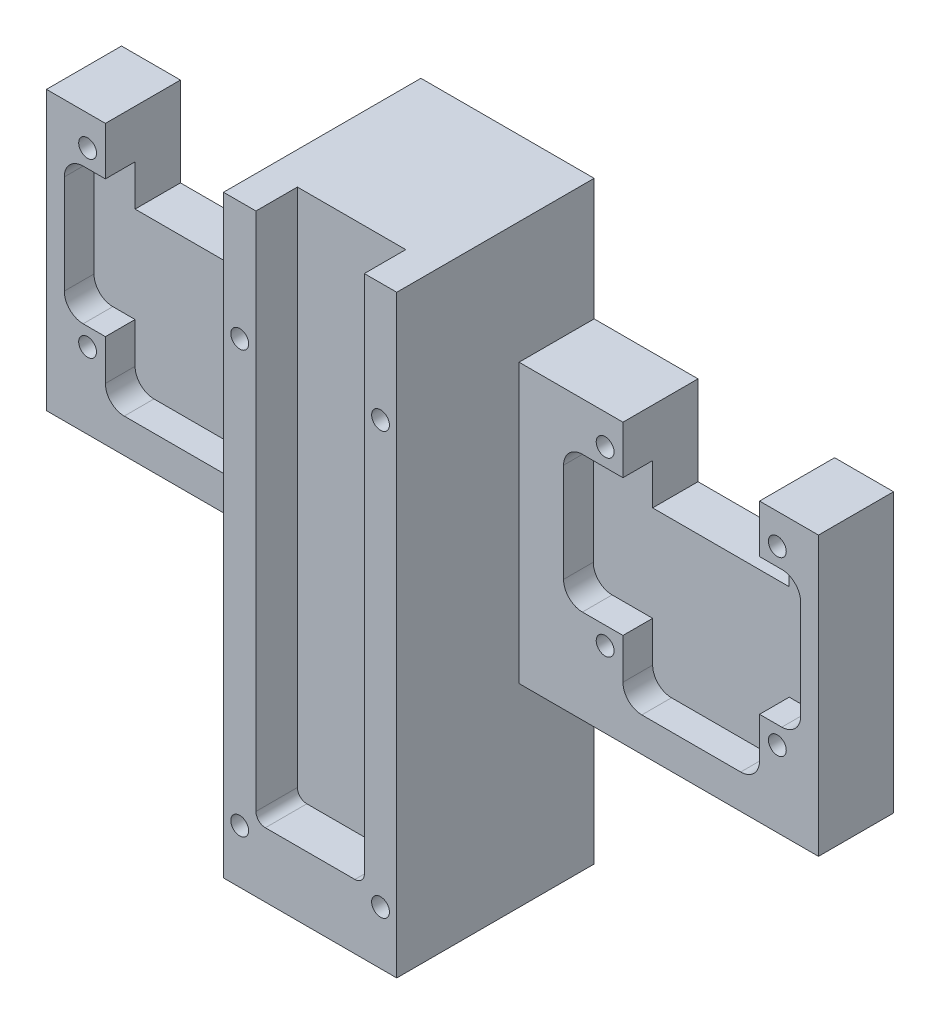
SolidWorks part; units mm, degrees
ref_plane "Front Plane" through (0, 0, 0) normal (0, 0, 1) x (1, 0, 0)
ref_plane "Top Plane" through (0, 0, 0) normal (0, 1, 0) x (1, 0, 0)
ref_plane "Right Plane" through (0, 0, 0) normal (1, 0, 0) x (0, 0, -1)
sketch "Sketch1" plane through (0, 0, 0) normal (0, 0, 1) x (1, 0, 0)
  line L0 (0, 0) -> (130, 0)
  line L1 (0, 0) -> (0, -104.86)
  line L2 (0, -104.86) -> (130, -104.86)
  line L3 (130, -104.86) -> (130, 0)
  dimension "D1" = 130
  dimension "D2" = 104.86
extrude "Boss-Extrude1" add sketch "Sketch1" along normal blind 39.84
sketch "Sketch2" plane through (0, 0, 39.84) normal (0, 0, 1) x (1, 0, 0)
  line L0 (130, 0) -> (130, -94.86)
  line L1 (130, -104.86) -> (130, 0) construction
  line L2 (130, -94.86) -> (0, -94.86)
  line L3 (0, 0) -> (0, -104.86) construction
  line L4 (0, -94.86) -> (0, 0)
  line L5 (0, 0) -> (130, 0)
  dimension "D1" = 94.86
extrude "Cut-Extrude1" cut sketch "Sketch2" against normal blind 6.6
sketch "Sketch3" plane through (0, 0, 33.24) normal (0, 0, 1) x (1, 0, 0)
  line L0 (55.875, 0) -> (55.875, -89.15)
  line L1 (130, 0) -> (0, 0) construction
  line L2 (55.875, -89.15) -> (74.125, -89.15)
  line L3 (74.125, -89.15) -> (74.125, 0)
  line L4 (74.125, 0) -> (55.875, 0)
  line L5 (130, -94.86) -> (130, 0) construction
  dimension "D1" = 18.25
  dimension "D2" = 55.875
  dimension "D3" = 89.15
extrude "Cut-Extrude2" cut sketch "Sketch3" against normal blind 6.98
sketch "Sketch5" plane through (0, 0, 33.24) normal (0, 0, 1) x (1, 0, 0)
  line L0 (79.585, 0) -> (79.585, -94.86)
  line L1 (130, 0) -> (74.125, 0) construction
  line L2 (0, -94.86) -> (130, -94.86) construction
  line L3 (79.585, -94.86) -> (130, -94.86)
  line L4 (130, -94.86) -> (130, 0)
  line L5 (130, 0) -> (79.585, 0)
  line L6 (50.415, 0) -> (50.415, -94.86)
  line L7 (55.875, 0) -> (0, 0) construction
  line L8 (50.415, -94.86) -> (0, -94.86)
  line L9 (0, -94.86) -> (0, 0)
  line L10 (0, 0) -> (50.415, 0)
  line L11 (55.875, 0) -> (55.875, -89.15) construction
  line L12 (74.125, -89.15) -> (74.125, 0) construction
  dimension "D1" = 5.46
  dimension "D2" = 5.46
extrude "Cut-Extrude3" cut sketch "Sketch5" against normal blind 20.6
sketch "Sketch6" plane through (0, 0, 12.64) normal (0, 0, 1) x (1, 0, 0)
  line L0 (50.415, -94.86) -> (50.415, 0) construction
  line L1 (74.125, 0) -> (55.875, 0) construction
  line L2 (79.585, 0) -> (79.585, -94.86) construction
  circle A0 centre (35.925, -25.6) radius 1.5
  circle A1 centre (6.925, -25.6) radius 1.5
  circle A2 centre (35.925, -54.6) radius 1.5
  circle A3 centre (6.925, -54.6) radius 1.5
  circle A4 centre (94.075, -25.6) radius 1.5
  circle A5 centre (123.075, -25.6) radius 1.5
  circle A6 centre (94.075, -54.6) radius 1.5
  circle A7 centre (123.075, -54.6) radius 1.5
  dimension "D2" = 3
  dimension "D3" = 25.6
  dimension "D4" = 29
  dimension "D5" = 29
  dimension "D6" = 29
  dimension "D8" = 14.49
  dimension "D9" = 29
  dimension "D10" = 29
  dimension "D11" = 29
  dimension "D1" = 14.49
  dimension "D7" = 29
  dimension "D12" = 29
  dimension "D13" = 25.6
extrude "Cut-Extrude4" cut sketch "Sketch6" against normal blind 12.4
sketch "Sketch7" plane through (0, 0, 12.64) normal (0, 0, 1) x (1, 0, 0)
  line L0 (50.415, -94.86) -> (50.415, 0) construction
  line L1 (0, 0) -> (50.415, 0)
  line L2 (0, 0) -> (0, -20.5)
  line L3 (0, -20.5) -> (50.415, -20.5)
  line L4 (50.415, 0) -> (50.415, -20.5)
  line L5 (130, -94.86) -> (130, 0) construction
  line L6 (79.585, 0) -> (130, 0)
  line L7 (79.585, 0) -> (79.585, -20.5)
  line L8 (79.585, -20.5) -> (130, -20.5)
  line L9 (130, 0) -> (130, -20.5)
  dimension "D1" = 20.5
  dimension "D2" = 20.5
extrude "Cut-Extrude5" cut sketch "Sketch7" against normal blind 12.4
sketch "Sketch9" plane through (0, 0, 12.64) normal (0, 0, 1) x (1, 0, 0)
  line L0 (97.075, -20.5) -> (97.075, -35.5)
  line L1 (79.585, -20.5) -> (130, -20.5) construction
  line L2 (97.075, -35.5) -> (120.075, -35.5)
  line L3 (120.075, -35.5) -> (120.075, -20.5)
  line L4 (120.075, -20.5) -> (97.075, -20.5)
  line L5 (9.925, -20.5) -> (9.925, -35.5)
  line L6 (0, -20.5) -> (50.415, -20.5) construction
  line L7 (9.925, -35.5) -> (32.925, -35.5)
  line L8 (32.925, -35.5) -> (32.925, -20.5)
  line L9 (0, -20.5) -> (50.415, -20.5) construction
  line L10 (32.925, -20.5) -> (9.925, -20.5)
  circle A0 centre (123.075, -25.6) radius 1.5 construction
  circle A1 centre (94.075, -25.6) radius 1.5 construction
  circle A2 centre (6.925, -25.6) radius 1.5 construction
  circle A3 centre (35.925, -25.6) radius 1.5 construction
  dimension "D1" = 3
  dimension "D4" = 3
  dimension "D2" = 3
  dimension "D3" = 15
  dimension "D5" = 3
  dimension "D6" = 15
extrude "Cut-Extrude7" cut sketch "Sketch9" against normal up to surface (12.4 mm away) up to face at (104.7925, -10.25, 0.24)
sketch "Sketch10" plane through (0, 0, 12.64) normal (0, 0, 1) x (1, 0, 0)
  line L0 (9.925, -28.6) -> (3, -28.6)
  line L1 (9.925, -35.5) -> (9.925, -20.5) construction
  line L2 (3, -28.6) -> (3, -51.6)
  line L3 (3, -51.6) -> (9.925, -51.6)
  line L4 (9.925, -51.6) -> (9.925, -61.6)
  line L5 (9.925, -61.6) -> (32.925, -61.6)
  line L6 (32.925, -61.6) -> (32.925, -51.6)
  line L7 (32.925, -51.6) -> (42.925, -51.6)
  line L8 (42.925, -51.6) -> (42.925, -28.6)
  line L9 (42.925, -28.6) -> (32.925, -28.6)
  line L10 (32.925, -35.5) -> (32.925, -20.5) construction
  line L11 (32.925, -28.6) -> (32.925, -35.5)
  line L12 (32.925, -35.5) -> (9.925, -35.5)
  line L13 (32.925, -35.5) -> (9.925, -35.5) construction
  line L14 (9.925, -35.5) -> (9.925, -28.6)
  line L16 (0, -20.5) -> (0, -94.86) construction
  line L17 (97.075, -28.6) -> (87.075, -28.6)
  line L18 (97.075, -20.5) -> (97.075, -35.5) construction
  line L19 (87.075, -28.6) -> (87.075, -51.6)
  line L20 (87.075, -51.6) -> (97.075, -51.6)
  line L21 (97.075, -51.6) -> (97.075, -61.6)
  line L22 (97.075, -61.6) -> (120.075, -61.6)
  line L23 (120.075, -61.6) -> (120.075, -51.6)
  line L24 (120.075, -51.6) -> (127, -51.6)
  line L25 (127, -51.6) -> (127, -28.6)
  line L26 (127, -28.6) -> (120.075, -28.6)
  line L27 (120.075, -35.5) -> (120.075, -20.5) construction
  line L28 (120.075, -28.6) -> (120.075, -35.5)
  line L29 (120.075, -35.5) -> (97.075, -35.5)
  line L30 (97.075, -35.5) -> (97.075, -28.6)
  line L31 (130, -94.86) -> (130, -20.5) construction
  circle A0 centre (6.925, -25.6) radius 1.5 construction
  circle A1 centre (35.925, -25.6) radius 1.5 construction
  circle A2 centre (6.925, -54.6) radius 1.5 construction
  circle A3 centre (6.925, -54.6) radius 1.5 construction
  circle A4 centre (35.925, -54.6) radius 1.5 construction
  circle A5 centre (94.075, -25.6) radius 1.5 construction
  circle A6 centre (94.075, -54.6) radius 1.5 construction
  circle A7 centre (123.075, -54.6) radius 1.5 construction
  circle A8 centre (123.075, -25.6) radius 1.5 construction
  dimension "D3" = 3
  dimension "D6" = 3
  dimension "D10" = 3
  dimension "D14" = 3
  dimension "D1" = 3
  dimension "D2" = 3
  dimension "D4" = 3
  dimension "D5" = 3
  dimension "D7" = 10
  dimension "D8" = 3
  dimension "D9" = 10
  dimension "D11" = 3
  dimension "D12" = 3
  dimension "D13" = 3
  dimension "D15" = 3
  dimension "D16" = 10
  dimension "D17" = 3
  dimension "D18" = 10
extrude "Cut-Extrude8" cut sketch "Sketch10" against normal blind 5
sketch "Sketch11" plane through (0, 0, 33.24) normal (0, 0, 1) x (1, 0, 0)
  line L0 (55.875, 0) -> (50.415, 0) construction
  line L1 (55.875, 0) -> (55.875, -89.15) construction
  line L2 (74.125, -89.15) -> (74.125, 0) construction
  line L3 (79.585, 0) -> (74.125, 0) construction
  circle A0 centre (53.145, -20) radius 1.5
  circle A1 centre (76.855, -20) radius 1.5
  circle A2 centre (53.145, -91) radius 1.5
  circle A3 centre (76.855, -91) radius 1.5
  point P4 (53.145, 0)
  dimension "D1" = 20
  dimension "D2" = 2.73
  dimension "D3" = 2.73
  dimension "D5" = 91
  dimension "D4" = 20
extrude "Cut-Extrude9" cut sketch "Sketch11" against normal blind 15
fillet "Fillet2" radius 3.175 1 edges at (3, -51.6, 10.14)
fillet "Fillet3" radius 3.175 15 edges at (120.075, -61.6, 10.14) (97.075, -61.6, 10.14) (127, -28.6, 10.14) (127, -51.6, 10.14) (87.075, -28.6, 10.14) (87.075, -51.6, 10.14) (79.585, -20.5, 6.44) (50.415, -20.5, 6.44) (32.925, -35.5, 3.94) (9.925, -35.5, 3.94) (3, -28.6, 10.14) (42.925, -28.6, 10.14) (42.925, -51.6, 10.14) (32.925, -61.6, 10.14) (9.925, -61.6, 10.14)
fillet "Fillet4" radius 3.175 2 edges at (120.075, -35.5, 3.94) (97.075, -35.5, 3.94)
fillet "Fillet5" radius 1.5875 2 edges at (74.125, -89.15, 29.75) (55.875, -89.15, 29.75)
fillet "Fillet6" radius 3.175 2 edges at (79.585, -94.86, 22.94) (50.415, -94.86, 22.94)
sketch "Sketch12" plane through (0, 0, 39.84) normal (0, 0, 1) x (1, 0, 0)
  line L0 (0, -67.36) -> (50.415, -67.36)
  line L1 (0, -20.5) -> (0, -94.86) construction
  line L2 (50.415, -91.685) -> (50.415, -17.325) construction
  line L3 (50.415, -67.36) -> (50.415, -95.14)
  line L4 (50.415, -95.14) -> (50.415, -104.86)
  line L5 (0, -104.86) -> (130, -104.86) construction
  line L6 (50.415, -104.86) -> (0, -104.86)
  line L7 (0, -104.86) -> (0, -67.36)
  line L8 (79.585, -67.36) -> (79.585, -104.86)
  line L9 (79.585, 0) -> (79.585, -91.685) construction
  line L10 (79.585, -104.86) -> (130, -104.86)
  line L11 (130, -104.86) -> (130, -67.36)
  line L12 (130, -94.86) -> (130, -20.5) construction
  line L13 (130, -67.36) -> (79.585, -67.36)
  line L14 (50.415, -100) -> (79.585, -100)
  line L15 (79.585, -100) -> (79.585, -104.86)
  line L16 (74.125, 0) -> (55.875, 0) construction
  line L17 (0, -20.5) -> (50.415, -20.5)
  line L18 (50.415, -20.5) -> (50.415, 0)
  line L19 (50.415, 0) -> (0, 0)
  line L20 (0, 0) -> (0, -20.5)
  line L21 (79.585, 0) -> (130, 0)
  line L22 (130, 0) -> (130, -20.5)
  line L23 (130, -20.5) -> (79.585, -20.5)
  line L24 (79.585, -17.325) -> (79.585, -91.685) construction
  line L25 (79.585, -20.5) -> (79.585, 0)
  line L26 (97.075, -20.5) -> (97.075, -35.5)
  line L27 (120.075, -20.5) -> (120.075, -35.5)
  line L28 (120.075, -35.5) -> (97.075, -35.5)
  line L29 (32.925, -20.5) -> (32.925, -35.5)
  line L30 (9.925, -20.5) -> (9.925, -35.5)
  line L31 (9.925, -35.5) -> (32.925, -35.5)
  line M6 (130, -94.86) -> (0, -94.86)
  line M7 (0, -94.86) -> (0, -104.86)
  line M8 (0, -104.86) -> (130, -104.86)
  line M9 (130, -104.86) -> (130, -94.86)
  dimension "D1" = 37.5
  dimension "D2" = 37.5
  dimension "D3" = 100
extrude "Cut-Extrude11" cut sketch "Sketch12" against normal blind 42 contours L19 L20 L17 L18 | L25 L23 L22 L21 | L28 L27 L23 L26 | L30 L31 L29 L17 | L7 L3 L0 M6 | L11 L13 L8 M6 | L8 M6 M8 M9 | L4 L3 M6 M7 M8 | L14 L4 L8 M8 region at (25.2075, -81.11, 39.84) region at (25.2075, -99.86, 39.84) region at (104.7925, -99.86, 39.84) region at (104.7925, -81.11, 39.84) region at (65, -102.43, 39.84) region at (25.2075, -10.25, 39.84) region at (21.425, -28, 39.84) region at (104.7925, -10.25, 39.84) region at (108.575, -28, 39.84)
sketch "Sketch13" plane through (79.585, 0, 0) normal (1, 0, 0) x (0, 0, -1)
  line L0 (-33.24, -94.86) -> (-33.24, -100)
  line L1 (0, -100) -> (-39.84, -100) construction
  line L2 (-33.24, -100) -> (-39.84, -100)
  line L3 (-39.84, -100) -> (-39.84, -94.86)
  line L4 (-39.84, -94.86) -> (-33.24, -94.86)
extrude "Cut-Extrude12" cut sketch "Sketch13" against normal through all
